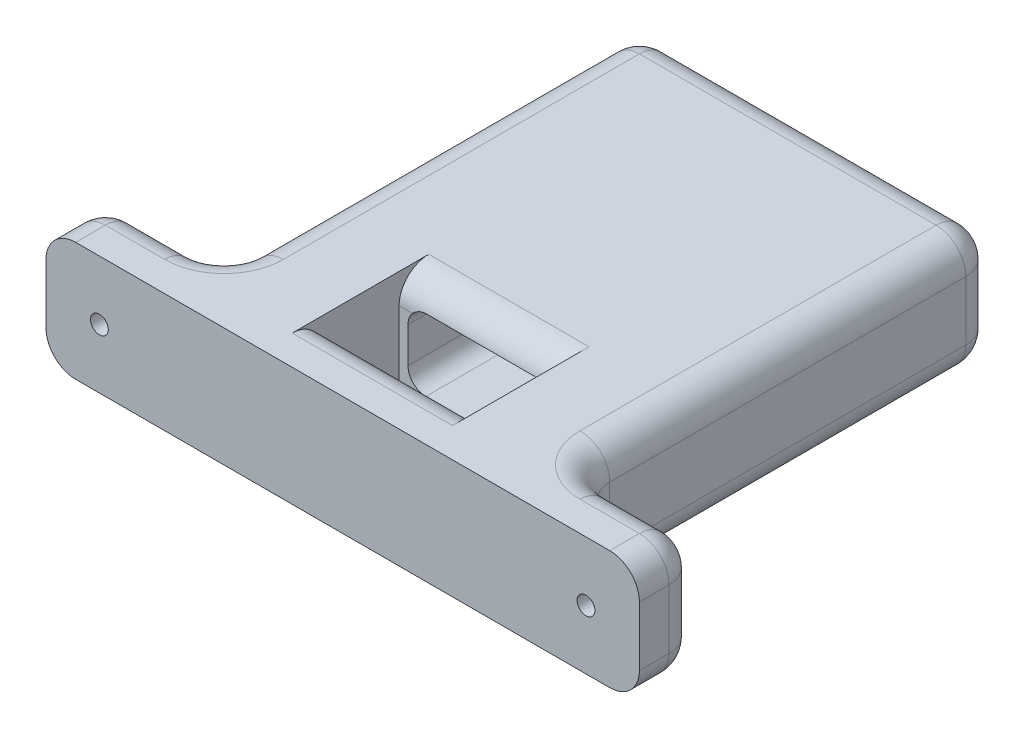
SolidWorks part; units mm, degrees
ref_plane "Plano frontal" through (0, 0, 0) normal (0, 0, 1) x (1, 0, 0)
ref_plane "Plano superior" through (0, 0, 0) normal (0, 1, 0) x (1, 0, 0)
ref_plane "Plano direito" through (0, 0, 0) normal (1, 0, 0) x (0, 0, -1)
sketch "Esboço1" plane through (0, 0, 0) normal (0, 0, 1) x (1, 0, 0)
  line L1 (-92.8694, -28.0887) -> (-32.8694, -28.0887)
  line L2 (-92.8694, -28.0887) -> (-92.8694, -8.0887)
  line L3 (-92.8694, -8.0887) -> (-32.8694, -8.0887)
  line L4 (-32.8694, -28.0887) -> (-32.8694, -8.0887)
  dimension "D1" = 20
  dimension "D2" = 60
extrude "Ressalto-extrusão1" add sketch "Esboço1" along normal blind 80
sketch "Esboço4" plane through (0, -28.0887, 0) normal (0, -1, 0) x (-1, 0, 0)
  line L0 (32.8694, -80) -> (32.8694, 0) construction
  line L1 (49.3694, -70) -> (76.3694, -70)
  line L2 (49.3694, -70) -> (49.3694, -57)
  line L3 (49.3694, -57) -> (76.3694, -57)
  line L4 (76.3694, -70) -> (76.3694, -57)
  line L7 (32.8694, -80) -> (92.8694, -80) construction
  point P4 (49.3694, -63.5)
  dimension "D1" = 27
  dimension "D2" = 13
  dimension "D3" = 16.5
  dimension "D4" = 10
extrude "Corte-extrusão2" cut sketch "Esboço4" against normal through all
sketch "Esboço5" plane through (-32.8694, 0, 0) normal (1, 0, 0) x (0, 0, -1)
  line L0 (-80, -8.0887) -> (0, -8.0887) construction
  line L1 (-80, -28.0887) -> (-70, -28.0887)
  line L2 (-80, -28.0887) -> (-80, -8.0887)
  line L3 (-80, -8.0887) -> (-70, -8.0887)
  line L4 (-70, -28.0887) -> (-70, -8.0887)
  dimension "D1" = 10
sketch "Esboço6" plane through (-92.8694, 0, 0) normal (-1, 0, 0) x (0, 0, 1)
  line L0 (80, -8.0887) -> (0, -8.0887) construction
  line L1 (80, -28.0887) -> (70, -28.0887)
  line L2 (80, -28.0887) -> (80, -8.0887)
  line L3 (80, -8.0887) -> (70, -8.0887)
  line L4 (70, -28.0887) -> (70, -8.0887)
  dimension "D1" = 10
extrude "Ressalto-extrusão2" add sketch "Esboço6" along normal blind 20
extrude "Ressalto-extrusão3" add sketch "Esboço5" along normal blind 20
sketch "Esboço7" plane through (0, 0, 0) normal (0, 0, -1) x (-1, 0, 0)
  line L0 (92.8694, -28.0887) -> (32.8694, -28.0887) construction
  line L1 (71.8694, -24.0887) -> (53.8694, -24.0887)
  line L2 (74.8694, -21.0887) -> (74.8694, -15.0887)
  line L3 (71.8694, -12.0887) -> (53.8694, -12.0887)
  line L4 (50.8694, -21.0887) -> (50.8694, -15.0887)
  line L5 (32.8694, -8.0887) -> (92.8694, -8.0887) construction
  line L6 (32.8694, -28.0887) -> (32.8694, -8.0887) construction
  line L7 (92.8694, -8.0887) -> (92.8694, -28.0887) construction
  arc A0 (74.8694, -15.0887) -> (71.8694, -12.0887) centre (71.8694, -15.0887) ccw
  arc A1 (53.8694, -12.0887) -> (50.8694, -15.0887) centre (53.8694, -15.0887) ccw
  arc A2 (53.8694, -24.0887) -> (50.8694, -21.0887) centre (53.8694, -21.0887) cw
  arc A3 (71.8694, -24.0887) -> (74.8694, -21.0887) centre (71.8694, -21.0887) ccw
  dimension "D5" = 3
  dimension "D1" = 4
  dimension "D2" = 4
  dimension "D3" = 18
  dimension "D4" = 18
extrude "Corte-extrusão4" cut sketch "Esboço7" against normal up to next
fillet "Filete1" radius 5 20 edges at (-102.8694, -8.0887, 70) (-22.8694, -28.0887, 70) (-22.8694, -8.0887, 70) (-12.8694, -8.0887, 75) (-112.8694, -8.0887, 75) (-112.8694, -28.0887, 75) (-12.8694, -28.0887, 75) (-112.8694, -18.0887, 70) (-102.8694, -28.0887, 70) (-92.8694, -18.0887, 70) (-12.8694, -18.0887, 70) (-32.8694, -18.0887, 70) (-32.8694, -28.0887, 35) (-32.8694, -8.0887, 35) (-92.8694, -8.0887, 35) (-92.8694, -28.0887, 35) (-62.8694, -28.0887, 0) (-92.8694, -18.0887, 0) (-62.8694, -8.0887, 0) (-32.8694, -18.0887, 0)
sketch "Esboço8" plane through (0, 0, 70) normal (0, 0, -1) x (-1, 0, 0)
  line L0 (17.8694, -23.0887) -> (27.8694, -23.0887) construction
  line L4 (97.8694, -13.0887) -> (97.8694, -23.0887) construction
  line L5 (97.8694, -23.0887) -> (107.8694, -23.0887) construction
  line L6 (27.8694, -23.0887) -> (27.8694, -13.0887) construction
  circle A0 centre (21.8694, -18.0887) radius 1.5
  circle A1 centre (103.8694, -18.0887) radius 1.5
  point P10 (27.8694, -18.0887)
  point P11 (97.8694, -18.0887)
  dimension "D1" = 3
  dimension "D2" = 3
  dimension "D3" = 5
  dimension "D4" = 6
  dimension "D5" = 6
  dimension "D6" = 5
extrude "Corte-extrusão5" cut sketch "Esboço8" against normal through all
fillet "Filete2" radius 5 2 edges at (-62.8694, -8.0887, 70) (-62.8694, -8.0887, 57)
